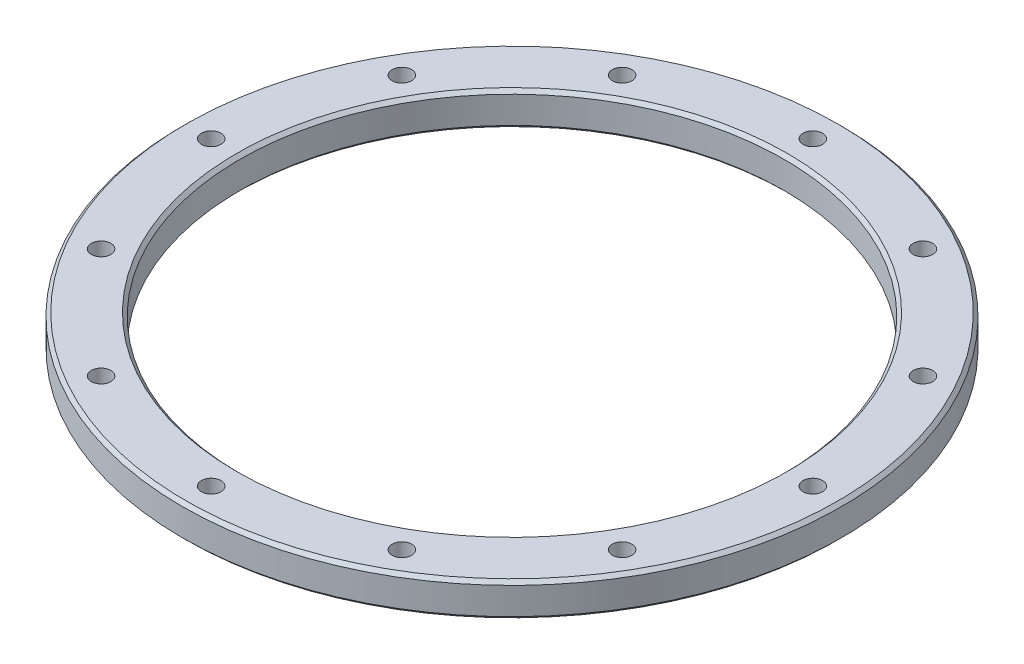
SolidWorks part; units mm, degrees
material "6061-T6 (SS)"
ref_plane "Front Plane" through (0, 0, 0) normal (0, 0, 1) x (1, 0, 0)
ref_plane "Top Plane" through (0, 0, 0) normal (0, 1, 0) x (1, 0, 0)
ref_plane "Right Plane" through (0, 0, 0) normal (1, 0, 0) x (0, 0, -1)
ref_plane "Plane1" through (0, 6.35, 0) normal (0, 1, 0) x (1, 0, 0)
sketch "Sketch1" plane through (0, 6.35, 0) normal (0, 1, 0) x (1, 0, 0)
  circle A0 centre (0, 0) radius 61.9125
  circle A1 centre (0, 0) radius 51.1175
extrude "Boss-Extrude1" add sketch "Sketch1" against normal blind 6.35
chamfer "Chamfer1" distance 0.635 angle 45 1 edges at (0, 0, -51.1175)
chamfer "Chamfer2" distance 0.635 angle 45 1 edges at (0, 6.35, -51.1175)
hole_wizard "Hole1" positions "Sketch3" profile "Sketch2" legacy
sketch "Sketch3" plane through (0, 0, 0) normal (0, -1, 0) x (-1, 0, 0)
  point P0 (28.2575, -48.9434)
sketch "Sketch2" plane through (-28.2575, 0, 48.9434) normal (1, 0, 0) x (0, 0, -1)
  line L0 (0, 0) -> (0, 6.35)
  line L1 (0, 6.35) -> (1.83, 6.35)
  line L2 (1.83, 6.35) -> (1.83, 0)
  line L3 (1.83, 0) -> (0, 0)
  line L4 (0, 110) -> (0, -10) construction
  dimension "Diameter" = 3.66
  dimension "Depth" = 6.35
sketch3d "3DSketch1"
  point P0 (0, -96.825, 0)
  point P1 (0, 3.175, 0)
ref_axis "Axis1" through (0, -96.825, 0) along (0, 1, 0)
pattern_circular "CirPattern1" count 12 over 360 about axis through (0, -96.825, 0) along (0, 1, 0) of "Hole1"
chamfer "Chamfer3" distance 0.635 angle 45 1 edges at (0, 0, -61.9125)
chamfer "Chamfer4" distance 0.635 angle 45 1 edges at (0, 6.35, -61.9125)
